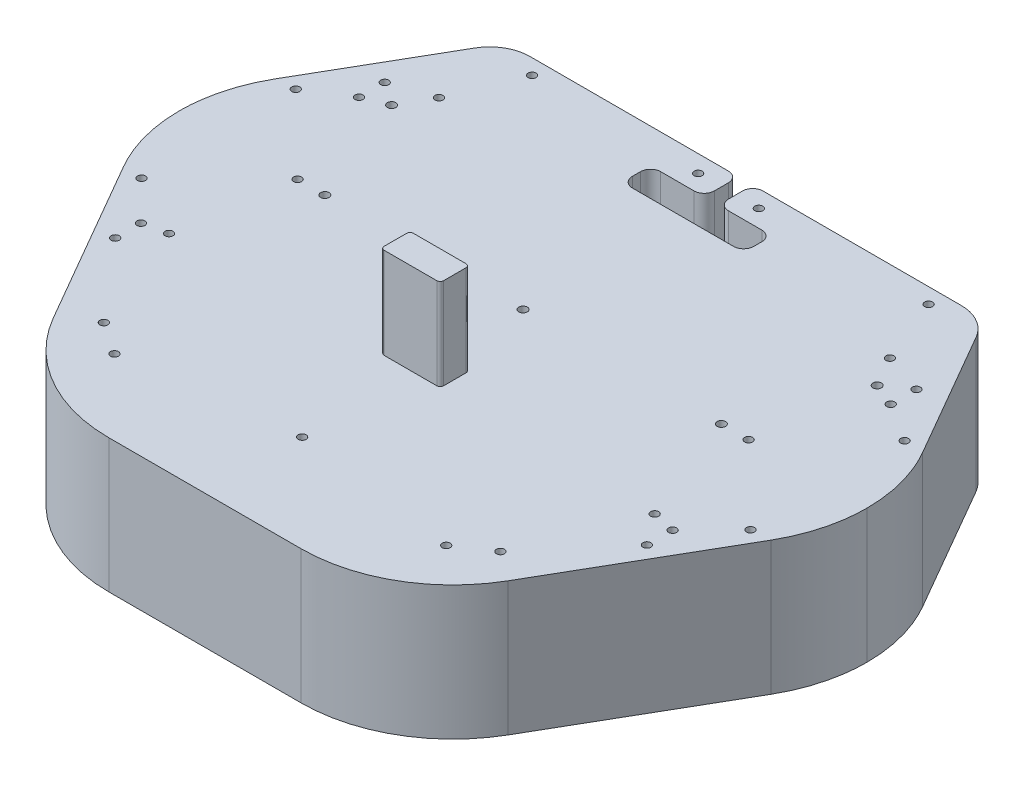
SolidWorks part; units mm, degrees
ref_plane "Front Plane" through (0, 0, 0) normal (0, 0, 1) x (1, 0, 0)
ref_plane "Top Plane" through (0, 0, 0) normal (0, 1, 0) x (1, 0, 0)
ref_plane "Right Plane" through (0, 0, 0) normal (1, 0, 0) x (0, 0, -1)
ref_plane "Plane1" through (0, 6, 0) normal (0, 1, 0) x (1, 0, 0)
sketch "Sketch1" plane through (0, 6, 0) normal (0, 1, 0) x (1, 0, 0)
  line L0 (118.094, 110) -> (-118.094, 110)
  line L1 (-118.094, 110) -> (-159.9519, 37.5)
  line L2 (-159.9519, -37.5) -> (-90.8013, -157.2724)
  line L3 (-90.8013, -157.2724) -> (90.8013, -157.2724)
  line L4 (90.8013, -157.2724) -> (159.9519, -37.5)
  line L5 (159.9519, 37.5) -> (118.094, 110)
  spline S0 degree 3 poles (-159.9519, 37.5) (-162.0898, 33.7968) (-165.8426, 25.7861) (-169.2445, 13.0899) (-169.9999, 4.2761) (-170, 0) knots 5.759587 5.759587 5.759587 5.759587 5.930629 6.112143 6.283185 6.283185 6.283185 6.283185
  spline S1 degree 3 poles (-170, 0) (-169.9999, -4.2761) (-169.2445, -13.0899) (-165.8426, -25.7861) (-162.0898, -33.7968) (-159.9519, -37.5) knots 0 0 0 0 0.171042 0.352557 0.523599 0.523599 0.523599 0.523599
  spline S2 degree 3 poles (159.9519, -37.5) (162.0898, -33.7968) (165.8426, -25.7861) (169.2445, -13.0899) (169.9999, -4.2761) (170, 0) knots 2.617994 2.617994 2.617994 2.617994 2.789036 2.97055 3.141593 3.141593 3.141593 3.141593
  spline S3 degree 3 poles (170, 0) (169.9999, 4.276) (169.2445, 13.0899) (165.8426, 25.7861) (162.0898, 33.7968) (159.9519, 37.5) knots 3.141593 3.141593 3.141593 3.141593 3.312635 3.494149 3.665191 3.665191 3.665191 3.665191
extrude "Boss-Extrude1" add sketch "Sketch1" against normal up to surface (66 mm away)
sketch "Sketch2" plane through (0, -60, 0) normal (0, -1, 0) x (1, 0, 0)
  line L0 (3.5, -110) -> (3.5, -93)
  line L1 (3.5, -93) -> (30, -93)
  line L2 (30, -93) -> (30, -79)
  line L3 (30, -79) -> (-30, -79)
  line L4 (-30, -79) -> (-30, -93)
  line L5 (-30, -93) -> (-3.5, -93)
  line L6 (-3.5, -93) -> (-3.5, -110)
  line L7 (-3.5, -110) -> (3.5, -110)
extrude "Cut-Extrude1" cut sketch "Sketch2" against normal through all
hole_wizard "M3.5 Clearance Hole1" positions "Sketch4" profile "Sketch3" hole size "M3.5" standard "ANSI Metric"
sketch "Sketch4" plane through (0, -60, 0) normal (0, -1, 0) x (-1, 0, 0)
  point P0 (0, -0.0015)
  point P1 (-97.9932, 0.0015)
  point P2 (97.9932, 0.0015)
  point P3 (120, 55.0015)
  point P4 (-120, 55.0015)
sketch "Sketch3" plane through (0, -60, 0.0015) normal (1, 0, 0) x (0, 0, -1)
  line L0 (0, 0) -> (0, 66.0001)
  line L1 (0, 66.0001) -> (2.0999, 66.0001)
  line L2 (2.0999, 66.0001) -> (2.0999, 0)
  line L5 (2.0999, 0) -> (0, 0)
  line L11 (0, -6.35) -> (0, 107.95) construction
  dimension "Thru Hole Dia." = 4.1998
  dimension "Thru Hole Depth" = 66.0001
hole_wizard "M3.5 Clearance Hole2" positions "Sketch6" profile "Sketch5" hole size "M3.5" standard "ANSI Metric"
sketch "Sketch6" plane through (0, -60, 0) normal (0, -1, 0) x (-1, 0, 0)
  point P0 (98, 102.4382)
  point P1 (0, -109.22)
  point P2 (98, -109.22)
  point P3 (-98, -109.22)
  point P4 (111.4552, 69.85)
  point P5 (111.4552, 0)
  point P6 (-111.4552, 69.85)
  point P7 (-111.4552, 0)
  point P8 (-120, -55)
  point P9 (120, -55)
  point P10 (131.4, 50.3)
  point P11 (-131.4, 50.3)
  point P12 (131.4, -70.2)
  point P13 (-131.4, -70.2)
  point P14 (131.4, 63)
  point P15 (-131.4, 63)
  point P16 (131.4, -57.5)
  point P17 (-131.4, -57.5)
  point P18 (15, 101.5)
  point P19 (-98, 102.4382)
  point P20 (-15, 101.5)
  point P21 (150.47, 38.1)
  point P22 (150.47, -38.1)
  point P23 (-150.47, 38.1)
  point P24 (-150.47, -38.1)
  point P25 (-82, -120)
  point P26 (82, -120)
sketch "Sketch5" plane through (-98, -60, -102.4382) normal (1, 0, 0) x (0, 0, -1)
  line L0 (0, 0) -> (0, 66.0001)
  line L1 (0, 66.0001) -> (1.9748, 66.0001)
  line L2 (1.9748, 66.0001) -> (1.9748, 0)
  line L5 (1.9748, 0) -> (0, 0)
  line L11 (0, -6.35) -> (0, 107.95) construction
  dimension "Thru Hole Dia." = 3.9496
  dimension "Thru Hole Depth" = 66.0001
fillet "Fillet1" radius 5.0247 8 edges at (-30, -27, -79) (30, -27, -79) (-30, -27, -93) (-3.5, -27, -93) (30, -27, -93) (3.5, -27, -93) tangent propagation no
fillet "Fillet2" radius 19.9245 2 edges at (118.094, -27, -110) (-118.094, -27, -110) tangent propagation no
fillet "Fillet3" radius 74.9585 2 edges at (-90.8013, -27, 157.2724) (90.8013, -27, 157.2724) tangent propagation no
sketch "Sketch7" plane through (0, 6, 0) normal (0, 1, 0) x (1, 0, 0)
  line L0 (-16.3908, -41.2673) -> (-16.4109, -52.2655)
  line L1 (-14.6904, -53.9915) -> (11.3096, -53.9915)
  line L3 (13.0302, -52.2655) -> (13.0101, -41.2673)
  line L4 (11.3096, -39.5022) -> (-14.6904, -39.5022)
  arc A0 (13.0101, -41.2673) -> (11.3096, -39.5022) centre (11.2403, -41.2706) ccw
  arc A1 (-14.6904, -39.5022) -> (-16.3908, -41.2673) centre (-14.6904, -41.2038) ccw
  arc A2 (-16.4109, -52.2655) -> (-14.6904, -53.9915) centre (-14.6904, -52.2709) ccw
  arc A3 (11.3096, -53.9915) -> (13.0302, -52.2655) centre (11.3096, -52.2709) ccw
extrude "Boss-Extrude2" add sketch "Sketch7" along normal up to surface (45 mm away)
